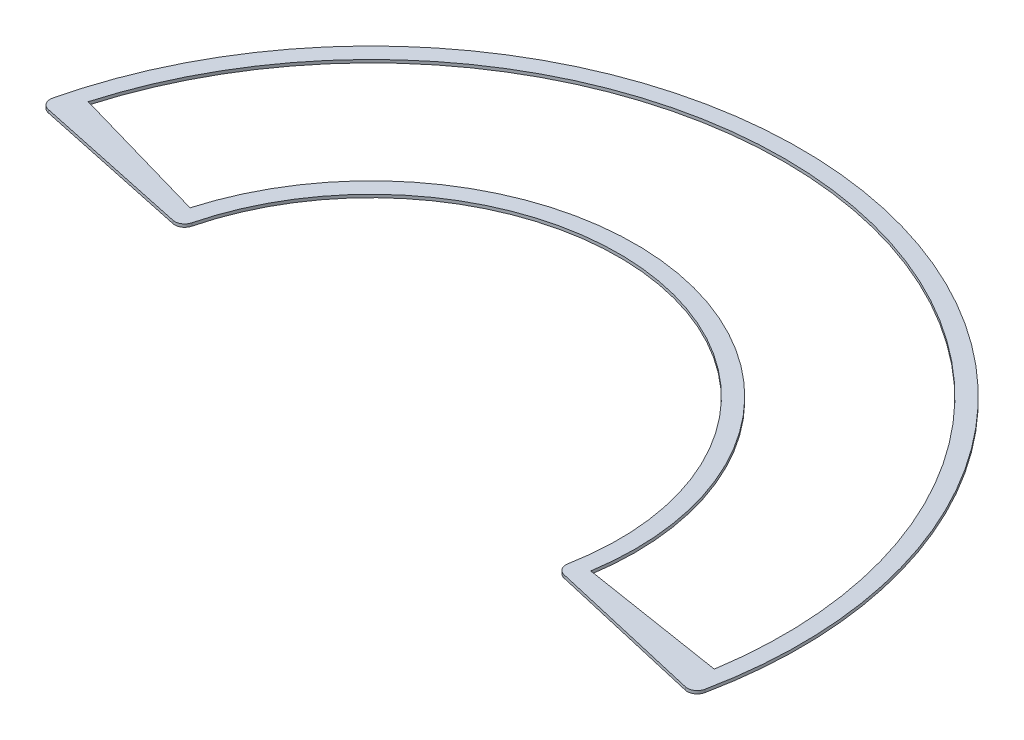
SolidWorks part; units mm, degrees
ref_plane "Front Plane" through (0, 0, 0) normal (0, 0, 1) x (1, 0, 0)
ref_plane "Top Plane" through (0, 0, 0) normal (0, 1, 0) x (1, 0, 0)
ref_plane "Right Plane" through (0, 0, 0) normal (1, 0, 0) x (0, 0, -1)
sketch "Sketch1" plane through (0, 0, 0) normal (0, 1, 0) x (1, 0, 0)
  line L0 (0, 75) -> (0, 130) construction
  line L1 (-76.2391, 16.2051) -> (-124.1901, 26.3974)
  line L2 (75.9446, -17.5332) -> (123.7105, -28.5608)
  line L3 (-76.9009, 22.051) -> (-120.1577, 34.4547)
  line L4 (0, 0) -> (-100.2146, 21.3013) construction
  line L5 (79.0151, -12.5148) -> (123.461, -19.5543)
  line L6 (0, 0) -> (99.8275, -23.047) construction
  line L7 (0, 0) -> (-98.5293, 28.2528) construction
  line L8 (0, 0) -> (101.2381, -16.0345) construction
  arc A0 (73.6726, -14.0482) -> (-72.707, 18.4034) centre (0, 0) ccw
  arc A1 (127.3236, -26.2433) -> (-126.4852, 30.0247) centre (0, 0) ccw
  arc A2 (123.7105, -28.5608) -> (127.3236, -26.2433) centre (124.3853, -25.6377) ccw
  arc A3 (73.6726, -14.0482) -> (75.9446, -17.5332) centre (76.6195, -14.6101) ccw
  arc A4 (-72.707, 18.4034) -> (-76.2391, 16.2051) centre (-75.6153, 19.1396) cw
  arc A5 (-124.1901, 26.3974) -> (-126.4852, 30.0247) centre (-123.5663, 29.3319) cw
  arc A6 (123.461, -19.5543) -> (-120.1577, 34.4547) centre (0, 0) ccw
  arc A7 (79.0151, -12.5148) -> (-76.9009, 22.051) centre (0, 0) ccw
  point P10 (126.6681, -29.2436)
  point P13 (73.0778, -16.8713)
  point P16 (-73.3611, 15.5934)
  point P19 (-127.1592, 27.0285)
  dimension "D7" = 3
  dimension "D2" = 130
  dimension "D8" = 125
  dimension "D5" = 75
  dimension "D6" = 80
  dimension "D1" = 78
  dimension "D3" = 103
  dimension "D4" = 99
  dimension "D9" = 74
base flange "Base-Flange1" sketch "Sketch1" thickness 0.9 reverse thickness direction no parameters "D1"=1
sketch "Bend-Lines1" [suppressed] plane through (0, 0, 0) normal (0, 1, 0) x (1, 0, 0)
sketch "Bounding-Box1" [suppressed] plane through (0, 0, 0) normal (0, 1, 0) x (1, 0, 0)
sheet metal parameters "Sheet-Metal1" thickness 0.9 parameters "D1"=1
flat pattern "Flat-Pattern1" [suppressed]
sketch "Bend-Lines2" plane through (0, 0, 0) normal (0, 1, 0) x (1, 0, 0)
sketch3d "Bounding-Box2" [suppressed]
  line L0 (-251.5295, 52.69, 0) -> (2.2794, -3.578, 0) construction
  line L1 (-223.1526, 180.6902, 0) -> (30.6563, 124.4221, 0) construction
  line L2 (-251.5295, 52.69, 0) -> (-223.1526, 180.6902, 0) construction
  line L3 (2.2794, -3.578, 0) -> (30.6563, 124.4221, 0) construction
equation "\"D6@Sketch1\"=\"D5@Sketch1\"+5"
equation "\"D8@Sketch1\"=\"D2@Sketch1\"-5"
equation "\"D3@Sketch1\"=\"D1@Sketch1\"+25"
equation "\"D4@Sketch1\"=\"D9@Sketch1\"+25"
